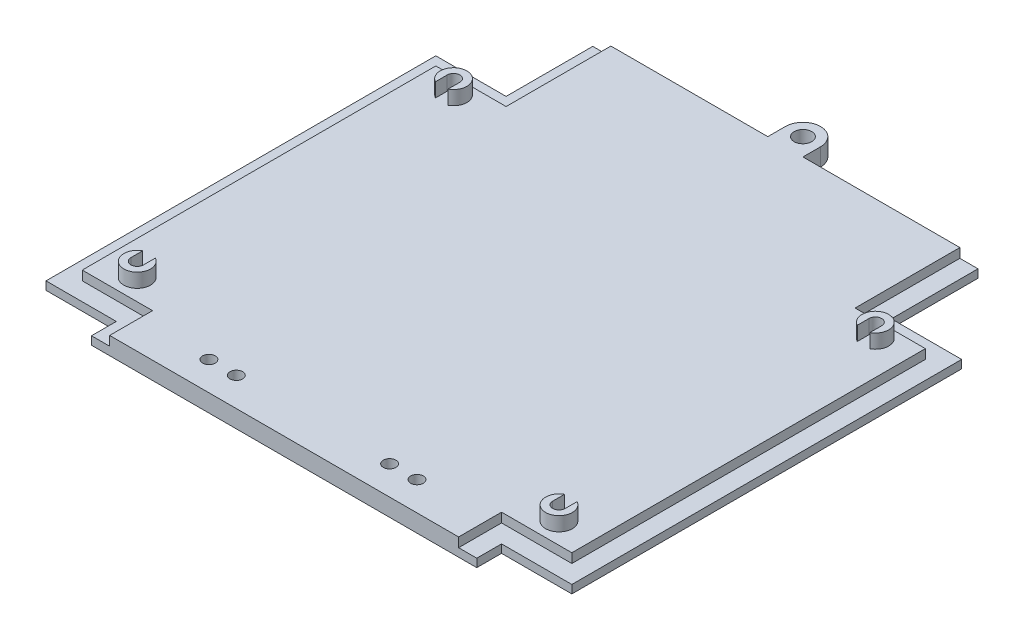
SolidWorks part; units mm, degrees
ref_plane "Front Plane" through (0, 0, 0) normal (0, 0, 1) x (1, 0, 0)
ref_plane "Top Plane" through (0, 0, 0) normal (0, 1, 0) x (1, 0, 0)
ref_plane "Right Plane" through (0, 0, 0) normal (1, 0, 0) x (0, 0, -1)
sketch "Sketch1" plane through (0, 0, 0) normal (0, 1, 0) x (1, 0, 0)
  line L0 (0, 149.7914) -> (0, 181.102)
  line L1 (0, 0) -> (139.192, 0)
  line L2 (0, 0) -> (0, 8.9586)
  line L3 (0, 181.102) -> (139.192, 181.102)
  line L4 (139.192, 0) -> (139.192, 8.9586)
  line L5 (0, 149.7914) -> (-25.4, 149.7914)
  line L7 (0, 8.9586) -> (-25.4, 8.9586)
  line L8 (-25.4, 149.7914) -> (-25.4, 8.9586)
  line L9 (139.192, 8.9586) -> (164.592, 8.9586)
  line L11 (139.192, 149.7914) -> (164.592, 149.7914)
  line L12 (164.592, 8.9586) -> (164.592, 149.7914)
  line L13 (139.192, 149.7914) -> (139.192, 181.102)
  dimension "D1" = 139.192
  dimension "D2" = 181.102
  dimension "D3" = 25.4
  dimension "D4" = 31.3106
  dimension "D5" = 8.9586
extrude "Boss-Extrude1" add sketch "Sketch1" along normal blind 6.35
sketch "Sketch2" plane through (0, 6.35, 0) normal (0, 1, 0) x (1, 0, 0)
  line L0 (69.596, 181.102) -> (69.596, 0) construction
  line L1 (139.192, 181.102) -> (0, 181.102) construction
  line L2 (0, 0) -> (139.192, 0) construction
  line L11 (132.642, 181.102) -> (132.642, 143.2414)
  line L12 (139.192, 181.102) -> (0, 181.102) construction
  line L13 (132.642, 143.2414) -> (158.042, 143.2414)
  line L14 (158.042, 143.2414) -> (158.042, 15.5086)
  line L15 (158.042, 15.5086) -> (132.642, 15.5086)
  line L16 (132.642, 15.5086) -> (132.642, 0)
  line L17 (132.642, 0) -> (139.192, 0)
  line L18 (139.192, 0) -> (139.192, 8.9586)
  line L19 (139.192, 8.9586) -> (164.592, 8.9586)
  line L20 (164.592, 8.9586) -> (164.592, 149.7914)
  line L21 (164.592, 149.7914) -> (139.192, 149.7914)
  line L22 (139.192, 149.7914) -> (139.192, 181.102)
  line L23 (139.192, 181.102) -> (132.642, 181.102)
  line L24 (0, 181.102) -> (6.55, 181.102)
  line L25 (0, 149.7914) -> (0, 181.102)
  line L26 (-25.4, 149.7914) -> (0, 149.7914)
  line L27 (-25.4, 8.9586) -> (-25.4, 149.7914)
  line L28 (0, 8.9586) -> (-25.4, 8.9586)
  line L29 (0, 0) -> (0, 8.9586)
  line L30 (6.55, 0) -> (0, 0)
  line L31 (6.55, 15.5086) -> (6.55, 0)
  line L32 (-18.85, 15.5086) -> (6.55, 15.5086)
  line L33 (-18.85, 143.2414) -> (-18.85, 15.5086)
  line L34 (6.55, 143.2414) -> (-18.85, 143.2414)
  line L35 (6.55, 181.102) -> (6.55, 143.2414)
  dimension "D1" = 6.55
  dimension "D2" = 6.55
  dimension "D3" = 6.55
  dimension "D4" = 6.55
  dimension "D5" = 6.55
extrude "Cut-Extrude1" cut sketch "Sketch2" against normal blind 3.375
sketch "Sketch3" plane through (0, 6.35, 0) normal (0, 1, 0) x (1, 0, 0)
  line L0 (132.642, 181.102) -> (6.55, 181.102) construction
  line L1 (63.246, 181.102) -> (75.946, 181.102)
  line L2 (63.246, 181.102) -> (63.246, 193.802)
  line L3 (63.246, 193.802) -> (75.946, 193.802)
  line L4 (75.946, 181.102) -> (75.946, 193.802)
  line L5 (139.192, 181.102) -> (0, 181.102) construction
  line L7 (139.192, 0) -> (139.192, 8.9586) construction
  line L8 (0, 177.292) -> (0, 0) construction
  point P6 (69.596, 181.102)
  point P9 (69.596, 181.102)
  dimension "D1" = 12.7
  dimension "D2" = 12.7
  dimension "D3" = 63.246
  dimension "D4" = 63.246
extrude "Boss-Extrude2" add sketch "Sketch3" against normal blind 6.35
fillet "Fillet1" radius 6.35 2 edges at (63.246, 3.175, -193.802) (75.946, 3.175, -193.802)
sketch "Sketch4" plane through (0, 6.35, 0) normal (0, 1, 0) x (1, 0, 0)
  circle A0 centre (69.596, 187.452) radius 3.175
  dimension "D1" = 6.35
extrude "Cut-Extrude2" cut sketch "Sketch4" against normal through all
sketch "Sketch5" plane through (0, 0, 0) normal (0, -1, 0) x (1, 0, 0)
  line L0 (107.188, -8.128) -> (107.188, 0) construction
  line L1 (0, 0) -> (139.192, 0) construction
  line L2 (109.474, -10.414) -> (139.192, -10.414) construction
  line L3 (139.192, 0) -> (139.192, -8.9586) construction
  line L4 (104.902, -10.414) -> (99.568, -10.414) construction
  line L5 (39.624, -10.414) -> (34.29, -10.414) construction
  line L7 (94.996, -10.414) -> (44.196, -10.414) construction
  line L8 (29.718, -10.414) -> (0, -10.414) construction
  line L9 (0, -8.9586) -> (0, 0) construction
  circle A0 centre (107.188, -10.414) radius 2.286
  circle A1 centre (97.282, -10.414) radius 2.286
  circle A2 centre (41.91, -10.414) radius 2.286
  circle A3 centre (32.004, -10.414) radius 2.286
  dimension "D2" = 4.572
  dimension "D3" = 4.572
  dimension "D4" = 4.572
  dimension "D5" = 4.572
  dimension "D1" = 8.128
  dimension "D6" = 5.334
  dimension "D7" = 5.334
  dimension "D8" = 50.8
extrude "Cut-Extrude3" cut sketch "Sketch5" against normal blind 12.7
sketch "Sketch6" plane through (0, 6.35, 0) normal (0, 1, 0) x (1, 0, 0)
  line L0 (-32.004, 181.864) -> (-32.004, -21.336) construction
  line L1 (-32.004, -21.336) -> (171.196, -21.336) construction
  line L2 (171.196, -21.336) -> (171.196, 181.864) construction
  line L3 (171.196, 181.864) -> (-32.004, 181.864) construction
  line L4 (6.55, 0) -> (132.642, 0) construction
  line L5 (132.642, 181.102) -> (75.946, 181.102) construction
  line L6 (-4.318, 23.114) -> (-4.318, 27.3642)
  line L7 (-8.89, 137.414) -> (-8.89, 133.1638)
  line L8 (-8.89, 27.3642) -> (-8.89, 23.114)
  line L9 (148.082, 23.114) -> (148.082, 27.3642)
  line L10 (-4.318, 133.1638) -> (-4.318, 137.414)
  line L11 (148.082, 137.414) -> (148.082, 133.1638)
  line L12 (143.51, 27.3642) -> (143.51, 23.114)
  line L14 (143.51, 133.1638) -> (143.51, 137.414)
  arc A0 (-4.318, 137.414) -> (-8.89, 137.414) centre (-6.604, 137.414) ccw
  arc A1 (148.082, 137.414) -> (143.51, 137.414) centre (145.796, 137.414) ccw
  arc A2 (143.51, 23.114) -> (148.082, 23.114) centre (145.796, 23.114) ccw
  arc A3 (-8.89, 23.114) -> (-4.318, 23.114) centre (-6.604, 23.114) ccw
  arc A4 (-4.318, 133.1638) -> (-8.89, 133.1638) centre (-6.604, 137.414) ccw
  arc A5 (148.082, 133.1638) -> (143.51, 133.1638) centre (145.796, 137.414) ccw
  arc A6 (143.51, 27.3642) -> (148.082, 27.3642) centre (145.796, 23.114) ccw
  arc A7 (-8.89, 27.3642) -> (-4.318, 27.3642) centre (-6.604, 23.114) ccw
  circle A8 centre (-6.604, 23.114) radius 4.826 construction
  circle A9 centre (-6.604, 23.114) radius 2.286 construction
  circle A10 centre (-6.604, 137.414) radius 2.286 construction
  circle A11 centre (-6.604, 137.414) radius 4.826 construction
  circle A12 centre (145.796, 23.114) radius 2.286 construction
  circle A13 centre (145.796, 23.114) radius 4.826 construction
  circle A14 centre (145.796, 137.414) radius 2.286 construction
  circle A15 centre (145.796, 137.414) radius 4.826 construction
  point P2 (69.596, -21.336)
  point P7 (69.596, 0)
  dimension "D4" = 4.572
  dimension "D1" = 0.762
  dimension "D2" = 203.2
  dimension "D3" = 203.2
  dimension "D5" = 44.45
  dimension "D6" = 44.45
  dimension "D7" = 25.4
  dimension "D8" = 25.4
  dimension "D9" = 2.54
extrude "Boss-Extrude3" add sketch "Sketch6" along normal blind 5.08
